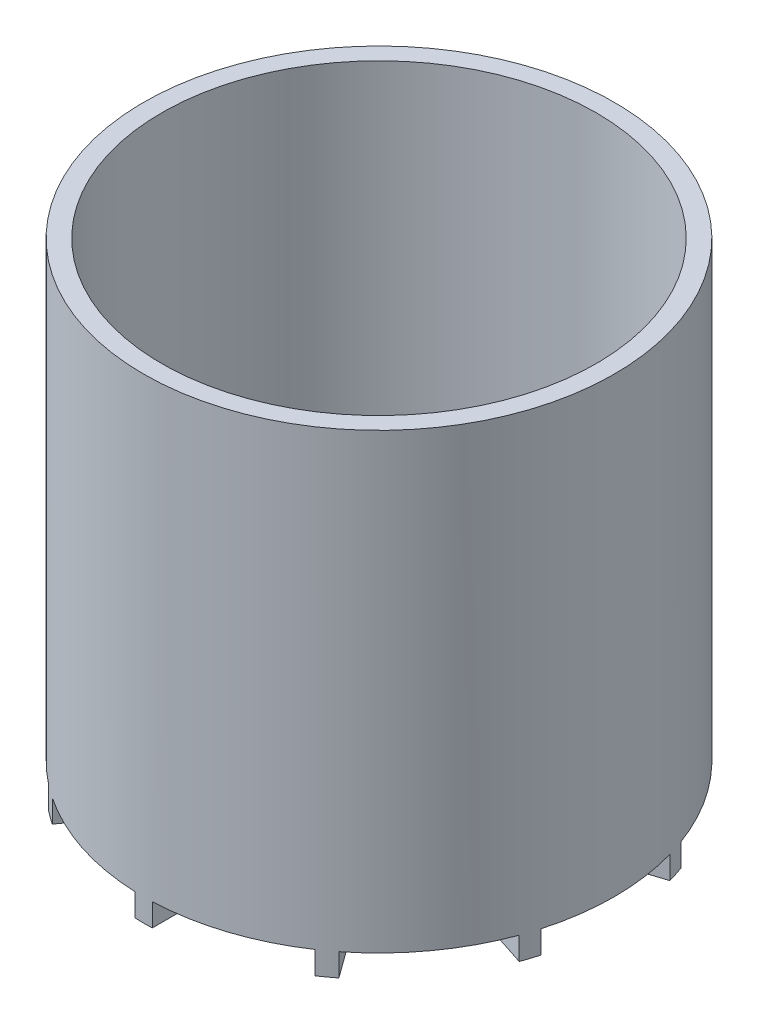
SolidWorks part; units mm, degrees
ref_plane "Front Plane" through (0, 0, 0) normal (0, 0, 1) x (1, 0, 0)
ref_plane "Top Plane" through (0, 0, 0) normal (0, 1, 0) x (1, 0, 0)
ref_plane "Right Plane" through (0, 0, 0) normal (1, 0, 0) x (0, 0, -1)
sketch "Sketch1" plane through (0, 0, 0) normal (0, 1, 0) x (1, 0, 0)
  circle A0 centre (0, 0) radius 38.1
  dimension "D1" = 76.2
extrude "Boss-Extrude1" add sketch "Sketch1" along normal blind 76.2
shell "Shell2" thickness 3.175 removed face at (0, 76.2, 38.1) outward yes
ref_axis "Axis1" through (0, 76.2, 0) along (0, -1, 0)
sketch "Sketch2" plane through (0, -3.175, 0) normal (0, -1, 0) x (-1, 0, 0)
  line L0 (0, 0) -> (0, 41.275)
  line L1 (-1.5, -41.275) -> (-1.5, 41.275)
  line L2 (-1.5, -41.275) -> (1.5, -41.275)
  line L3 (-1.5, 41.275) -> (1.5, 41.275)
  line L4 (1.5, -41.275) -> (1.5, 41.275)
  line L5 (-1.5, -41.275) -> (1.5, 41.275) construction
  line L6 (-1.5, 41.275) -> (1.5, -41.275) construction
  line L7 (-23.0473, -34.2739) -> (25.4744, 32.5105)
  line L8 (-25.4744, -32.5105) -> (23.0473, 34.2739)
  line L9 (-25.4744, -32.5105) -> (-23.0473, -34.2739)
  line L10 (23.0473, 34.2739) -> (25.4744, 32.5105)
  line L11 (-38.7913, -14.1813) -> (39.7184, 11.3281)
  line L12 (-39.7184, -11.3281) -> (38.7913, 14.1813)
  line L13 (-39.7184, -11.3281) -> (-38.7913, -14.1813)
  line L14 (38.7913, 14.1813) -> (39.7184, 11.3281)
  line L15 (-39.7184, 11.3281) -> (38.7913, -14.1813)
  line L16 (-38.7913, 14.1813) -> (39.7184, -11.3281)
  line L17 (-38.7913, 14.1813) -> (-39.7184, 11.3281)
  line L18 (39.7184, -11.3281) -> (38.7913, -14.1813)
  line L19 (-25.4744, 32.5105) -> (23.0473, -34.2739)
  line L20 (-23.0473, 34.2739) -> (25.4744, -32.5105)
  line L21 (-23.0473, 34.2739) -> (-25.4744, 32.5105)
  line L22 (25.4744, -32.5105) -> (23.0473, -34.2739)
  line L23 (-1.5, 41.275) -> (-1.5, -41.275)
  line L24 (1.5, 41.275) -> (1.5, -41.275)
  line L25 (1.5, 41.275) -> (-1.5, 41.275)
  line L26 (1.5, -41.275) -> (-1.5, -41.275)
  circle A1 centre (0, 0) radius 41.275 construction
  circle A2 centre (0, 0) radius 41.275
  dimension "D1" = 3
  dimension "D2" = 6
extrude "Boss-Extrude2" add sketch "Sketch2" along normal blind 4 contours L4 L3 L1 L2 | L7 L10 L8 L9 | L11 L14 L12 L13 | L15 L18 L16 L17 | L20 L22 L19 L21
sketch "Sketch3" plane through (0, -3.175, 0) normal (0, -1, 0) x (1, 0, 0)
  circle A0 centre (0, 0) radius 41.275
  circle A1 centre (0, 0) radius 61.9063
extrude "Cut-Extrude1" cut sketch "Sketch3" against normal through all both and the other way through all
